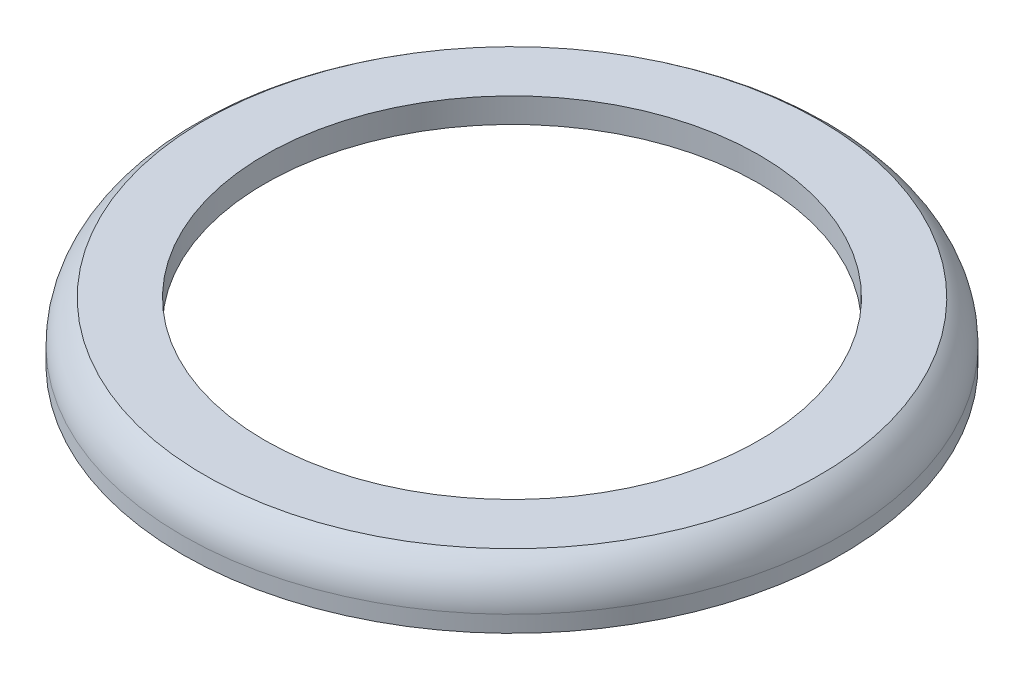
SolidWorks part; units mm, degrees
material "ASTM A36 Acero"
ref_plane "Alzado" through (0, 0, 0) normal (0, 0, 1) x (1, 0, 0)
ref_plane "Planta" through (0, 0, 0) normal (0, 1, 0) x (1, 0, 0)
ref_plane "Vista lateral" through (0, 0, 0) normal (1, 0, 0) x (0, 0, -1)
sketch "Croquis1" plane through (0, 0, 0) normal (0, 0, 1) x (1, 0, 0)
  line L0 (0, 0) -> (18.5, 0) construction
  line L1 (20, 0) -> (20, 1)
  line L2 (18.6583, 3.5) -> (15, 3.5)
  line L3 (15, 3.5) -> (15, 2)
  line L4 (15, 2) -> (19, 2)
  line L5 (19, 2) -> (19, 1)
  line L6 (19, 1) -> (18.5, 1)
  line L7 (18.5, 1) -> (18.5, 0)
  line L8 (0, 0) -> (0, 3.5) construction
  line L9 (18.5, 0) -> (20, 0)
  arc A0 (20, 1) -> (18.6583, 3.5) centre (17, 1) ccw
  dimension "D7" = 3
  dimension "D1" = 0.5
  dimension "D2" = 1
  dimension "D3" = 1
  dimension "D4" = 20
  dimension "D5" = 15
  dimension "D6" = 1.5
  dimension "D8" = 1
revolve "Revolución1" add sketch "Croquis1" angle 360 about L8
fillet "Redondeo1" radius 0.25 4 edges at (0, 1, -19) (0, 0, -18.5) (0, 1, -18.5) (0, 2, -19)
